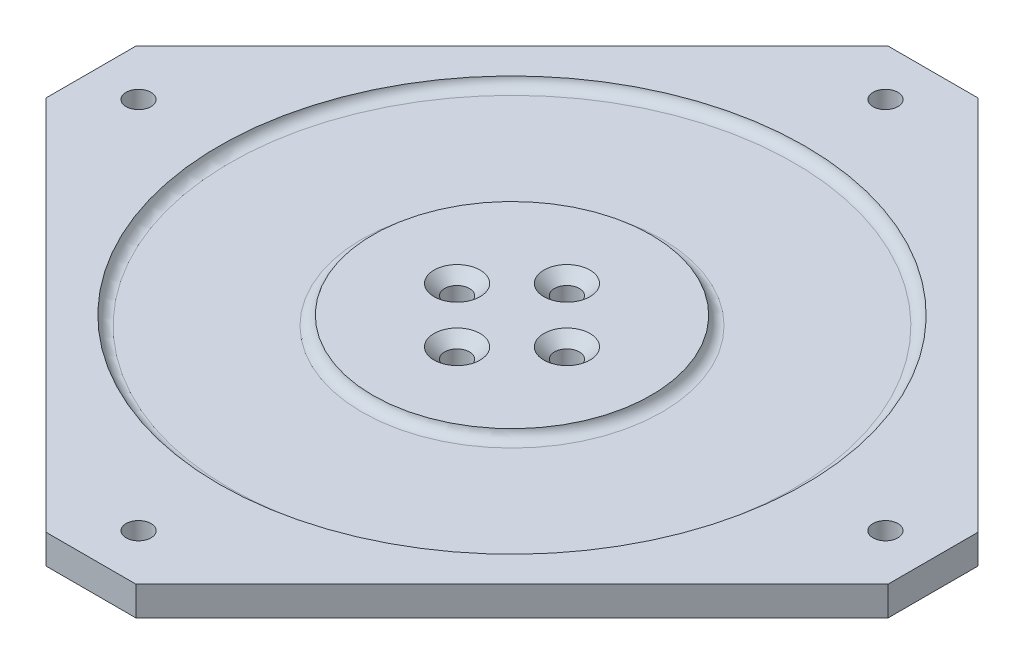
SolidWorks part; units mm, degrees
material "6061-T6 (SS)"
ref_plane "Front Plane" through (0, 0, 0) normal (0, 0, 1) x (1, 0, 0)
ref_plane "Top Plane" through (0, 0, 0) normal (0, 1, 0) x (1, 0, 0)
ref_plane "Right Plane" through (0, 0, 0) normal (1, 0, 0) x (0, 0, -1)
sketch "Sketch1" plane through (0, 0, 0) normal (0, 1, 0) x (1, 0, 0)
  line L0 (-63.6396, 0) -> (0, -63.6396)
  line L1 (-63.6396, 0) -> (0, 63.6396)
  line L2 (0, -63.6396) -> (63.6396, 0)
  line L3 (0, 63.6396) -> (63.6396, 0)
  line L4 (-63.6396, 0) -> (63.6396, 0) construction
  line L5 (0, -63.6396) -> (0, 63.6396) construction
  line L6 (-49.4975, 0) -> (0, 49.4975) construction
  line L7 (0, 49.4975) -> (49.4975, 0) construction
  line L8 (0, -49.4975) -> (49.4975, 0) construction
  line L9 (-49.4975, 0) -> (0, -49.4975) construction
  point P1 (0, 0)
  dimension "D1" = 90
  dimension "D2" = 10
extrude "Mounting base" add sketch "Sketch1" along normal blind 4
sketch "Sketch16" plane through (0, 4, 0) normal (0, 1, 0) x (1, 0, 0)
  line L0 (-7.5, 0) -> (0, -7.5) construction
  line L1 (-7.5, 0) -> (0, 7.5) construction
  line L2 (0, -7.5) -> (7.5, 0) construction
  line L3 (0, 7.5) -> (7.5, 0) construction
  line L4 (-7.5, 0) -> (7.5, 0) construction
  line L5 (0, -7.5) -> (0, 7.5) construction
  point P1 (0, 0)
  point P2 (0, 7.5)
  point P3 (7.5, 0)
  point P9 (0, -7.5)
  point P10 (-7.5, 0)
  dimension "D1" = 15
hole_wizard "CSK for M3 Flat Head Machine Screw2" positions "Sketch21" profile "Sketch20" countersink size "M3" standard "ANSI Metric"
sketch "Sketch21" plane through (0, 0, 0) normal (0, -1, 0) x (-1, 0, 0)
  line L0 (-51, 0) -> (0, 0) construction
  line L1 (0, 0) -> (51, 0) construction
  line L4 (0, 51) -> (0, 0) construction
  line L5 (0, 0) -> (0, -51) construction
  point P0 (51, 0)
  point P2 (0, -51)
  point P4 (-51, 0)
  point P6 (0, 51)
  dimension "D1" = 51
sketch "Sketch20" plane through (-51, 0, 0) normal (1, 0, 0) x (0, 0, -1)
  line L0 (0, 0) -> (0, 5.0215)
  line L1 (0, 5.0215) -> (1.7, 4)
  line L2 (1.7, 4) -> (1.7, 1.45)
  line L3 (1.7, 1.45) -> (3.15, 0)
  line L5 (3.15, 0) -> (0, 0)
  line L6 (-1.7, 1.45) -> (-3.15, 0) construction
  line L10 (0, 5.0215) -> (-1.7, 4) construction
  line L11 (0, -6.35) -> (0, 107.95) construction
  dimension "Hole Dia." = 3.4
  dimension "Hole Depth" = 4
  dimension "Near C'Sink Dia." = 6.3
  dimension "Near C'Sink Angle" = 90
  dimension "Drill Angle" = 118
hole_wizard "CSK for M3 Flat Head Machine Screw1" positions "3DSketch1" profile "Sketch17" countersink size "M3" standard "ANSI Metric" end condition through all
sketch3d "3DSketch1"
  point P0 (0, 4, -7.5)
  point P3 (7.5, 4, 0)
  point P6 (0, 4, 7.5)
  point P9 (-7.5, 4, 0)
sketch "Sketch17" plane through (0, 4, -7.5) normal (1, 0, 0) x (0, 0, 1)
  line L0 (0, 0) -> (0, 4)
  line L1 (0, 4) -> (1.7, 4)
  line L2 (1.7, 4) -> (1.7, 1.45)
  line L3 (1.7, 1.45) -> (3.15, 0)
  line L5 (3.15, 0) -> (0, 0)
  line L6 (-1.7, 1.45) -> (-3.15, 0) construction
  line L11 (0, -6.35) -> (0, 107.95) construction
  dimension "Thru Hole Dia." = 3.4
  dimension "Thru Hole Depth" = 4
  dimension "Near C'Sink Dia." = 6.3
  dimension "Near C'Sink Angle" = 90
sketch "Sketch12" plane through (0, 0, 0) normal (0, 1, 0) x (1, 0, 0)
  line L1 (-57.5, -57.5) -> (57.5, -57.5)
  line L2 (-57.5, -57.5) -> (-57.5, 57.5)
  line L3 (-57.5, 57.5) -> (57.5, 57.5)
  line L4 (57.5, -57.5) -> (57.5, 57.5)
  line L5 (0, 57.5) -> (0, -57.5) construction
  line L6 (-57.5, 0) -> (57.5, 0) construction
  point P0 (0, 0)
  dimension "D1" = 115
  dimension "D2" = 115
extrude "Cut-Extrude2" cut sketch "Sketch12" along normal blind 20 flip side to cut
sketch "Sketch19" plane through (0, 4, 0) normal (0, 1, 0) x (1, 0, 0)
  line L1 (40, 16.5685) -> (16.5685, 40)
  line L2 (16.5685, 40) -> (-16.5685, 40)
  line L3 (-16.5685, 40) -> (-40, 16.5685)
  line L4 (-40, 16.5685) -> (-40, -16.5685)
  line L5 (-40, -16.5685) -> (-16.5685, -40)
  line L6 (-16.5685, -40) -> (16.5685, -40)
  line L7 (16.5685, -40) -> (40, -16.5685)
  line L8 (40, -16.5685) -> (40, 16.5685)
  line L9 (19, 7.8701) -> (7.8701, 19) construction
  line L10 (7.8701, 19) -> (-7.8701, 19) construction
  line L11 (-7.8701, 19) -> (-19, 7.8701) construction
  line L12 (-19, 7.8701) -> (-19, -7.8701) construction
  line L13 (-19, -7.8701) -> (-7.8701, -19) construction
  line L14 (-7.8701, -19) -> (7.8701, -19) construction
  line L15 (7.8701, -19) -> (19, -7.8701) construction
  line L16 (19, -7.8701) -> (19, 7.8701) construction
  circle A0 centre (0, 0) radius 40
  circle A1 centre (0, 0) radius 19
  dimension "D1" = 21
  dimension "D2" = 80
extrude "Cut-Extrude4" cut sketch "Sketch19" against normal blind 1.25 contours A0 A1 region at (35.9099, 4, -14.8744)
extrude "Cut-Extrude5" cut sketch "Sketch19<3>" along normal blind 1.25 from surface contours A0 A1 region at (35.9099, 4, -14.8744) starting at face at (0, 0, 0)
sketch "Sketch19<3>" plane through (0, 4, 0) normal (0, 1, 0) x (1, 0, 0) same geometry as "Sketch19"
fillet "Fillet1" radius 1.5 4 edges at (0, 1.25, -40) (0, 1.25, -19) (0, 2.75, 40) (0, 2.75, 19)
sketch "Sketch9" plane through (0, 0, 0) normal (0, 0, 1) x (1, 0, 0)
  line L0 (0, 0) -> (0, 7.5998) construction
ref_axis "Axis1" through (0, 0, 0) along (0, 1, 0)
sketch "Sketch10" plane through (0, 4, 0) normal (0, 1, 0) x (1, 0, 0)
  line L0 (-2.25, 33.55) -> (2.25, 33.55)
  line L1 (-33.55, -2.25) -> (-26.45, -2.25)
  line L2 (-33.55, -2.25) -> (-33.55, 2.25)
  line L3 (-33.55, 2.25) -> (-26.45, 2.25)
  line L4 (-26.45, -2.25) -> (-26.45, 2.25)
  line L5 (-30, 2.25) -> (-30, -2.25) construction
  line L6 (-33.55, 0) -> (-26.45, 0) construction
  line L7 (2.25, 33.55) -> (2.25, 26.45)
  line L8 (-2.25, 26.45) -> (2.25, 26.45)
  line L9 (-2.25, 33.55) -> (-2.25, 26.45)
  line L10 (2.25, 30) -> (-2.25, 30) construction
  line L11 (0, 33.55) -> (0, 26.45) construction
  line L12 (33.55, 2.25) -> (33.55, -2.25)
  line L13 (33.55, -2.25) -> (26.45, -2.25)
  line L14 (26.45, 2.25) -> (26.45, -2.25)
  line L15 (33.55, 2.25) -> (26.45, 2.25)
  line L16 (30, -2.25) -> (30, 2.25) construction
  line L17 (33.55, 0) -> (26.45, 0) construction
  line L18 (2.25, -33.55) -> (-2.25, -33.55)
  line L19 (-2.25, -33.55) -> (-2.25, -26.45)
  line L20 (2.25, -26.45) -> (-2.25, -26.45)
  line L21 (2.25, -33.55) -> (2.25, -26.45)
  line L22 (-2.25, -30) -> (2.25, -30) construction
  line L23 (0, -33.55) -> (0, -26.45) construction
  line L24 (0, 0) -> (-26.45, 0) construction
  point P14 (0, 30)
  point P21 (30, 0)
  point P30 (0, -30)
  point P136 (-30, 0)
  dimension "D1" = 4.5
  dimension "D2" = 7.1
  dimension "D3" = 30
  dimension "D4" = 4
